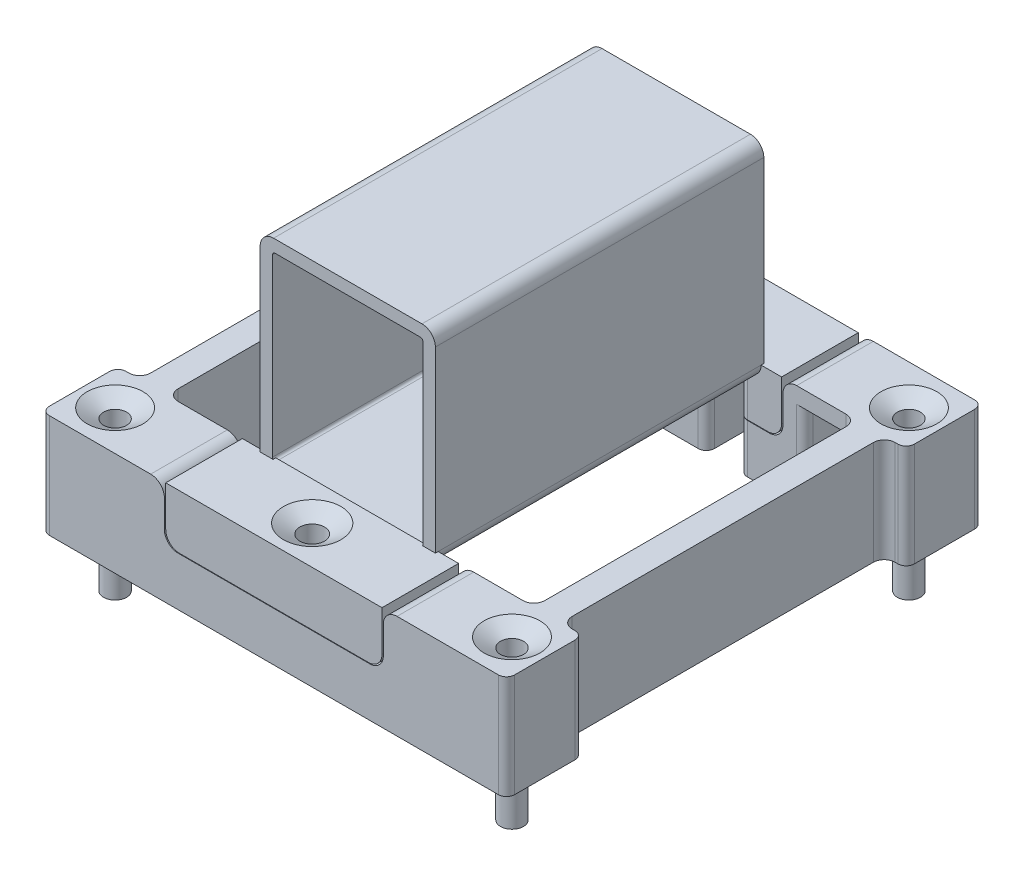
SolidWorks part; units mm, degrees
ref_plane "Front Plane" through (0, 0, 0) normal (0, 0, 1) x (1, 0, 0)
ref_plane "Top Plane" through (0, 0, 0) normal (0, 1, 0) x (1, 0, 0)
ref_plane "Right Plane" through (0, 0, 0) normal (1, 0, 0) x (0, 0, -1)
sketch "Sketch1" plane through (0, 0, 0) normal (0, 0, 1) x (1, 0, 0)
  line L0 (14.75, -16.3) -> (14.75, 16.3) construction
  line L1 (13.55, -17.5) -> (-13.55, -17.5) construction
  line L2 (-14.75, -16.3) -> (-14.75, 16.3) construction
  line L3 (13.55, 17.5) -> (-13.55, 17.5) construction
  line L4 (14.75, -16.3) -> (14.75, 16.3)
  line L5 (13.55, -17.5) -> (-13.55, -17.5)
  line L6 (-14.75, -16.3) -> (-14.75, 16.3)
  line L7 (13.55, 17.5) -> (-13.55, 17.5)
  line L8 (13.5, -16.25) -> (13.5, 16.25) construction
  line L9 (13.5, -16.25) -> (-13.5, -16.25) construction
  line L10 (-13.5, -16.25) -> (-13.5, 16.25) construction
  line L11 (13.5, 16.25) -> (-13.5, 16.25) construction
  line L12 (13.5, -16.25) -> (13.5, 16.25) construction
  line L13 (13.5, -16.25) -> (-13.5, -16.25) construction
  line L14 (-13.5, -16.25) -> (-13.5, 16.25) construction
  line L15 (13.5, 16.25) -> (-13.5, 16.25) construction
  line L16 (13.75, -16.5) -> (13.75, 16.5)
  line L17 (13.75, 16.5) -> (-13.75, 16.5)
  line L18 (-13.75, -16.5) -> (-13.75, 16.5)
  line L19 (13.75, -16.5) -> (-13.75, -16.5)
  arc A0 (14.75, 16.3) -> (13.55, 17.5) centre (13.55, 16.3) ccw construction
  arc A1 (13.55, -17.5) -> (14.75, -16.3) centre (13.55, -16.3) ccw construction
  arc A2 (-14.75, -16.3) -> (-13.55, -17.5) centre (-13.55, -16.3) ccw construction
  arc A3 (-13.55, 17.5) -> (-14.75, 16.3) centre (-13.55, 16.3) ccw construction
  arc A4 (14.75, 16.3) -> (13.55, 17.5) centre (13.55, 16.3) ccw
  arc A5 (13.55, -17.5) -> (14.75, -16.3) centre (13.55, -16.3) ccw
  arc A6 (-14.75, -16.3) -> (-13.55, -17.5) centre (-13.55, -16.3) ccw
  arc A7 (-13.55, 17.5) -> (-14.75, 16.3) centre (-13.55, 16.3) ccw
  dimension "D1" = 0.25
extrude "Boss-Extrude1" add sketch "Sketch1" along normal mid plane 60
sketch "Sketch2" plane through (0, 0, 0) normal (1, 0, 0) x (0, 0, -1)
  line L0 (-29.5, -24.25) -> (-29.5, 24.25) construction
  line L1 (-29.5, -16.3) -> (-43.5, -16.3)
  line L2 (-29.5, -16.3) -> (-29.5, -35.25)
  line L3 (-29.5, -35.25) -> (-43.5, -35.25)
  line L4 (-43.5, -16.3) -> (-43.5, -35.25)
  line L5 (-30, -16.3) -> (30, -16.3) construction
  line L6 (-29.5, -29.25) -> (29.5, -29.25) construction
  line L8 (-43.5, -15.125) -> (-43.5, 15.125) construction
  line L9 (0, 0) -> (0, -45.8115) construction
  line L10 (0, -15.125) -> (0, 15.125) construction
  line L11 (29.5, -35.25) -> (43.5, -35.25)
  line L12 (43.5, -16.3) -> (43.5, -35.25)
  line L13 (29.5, -16.3) -> (43.5, -16.3)
  line L14 (29.5, -16.3) -> (29.5, -35.25)
  dimension "D1" = 6
extrude "Boss-Extrude2" add sketch "Sketch2" along normal mid plane 85
sketch "Sketch3" plane through (0, -35.25, 0) normal (0, -1, 0) x (1, 0, 0)
  line L0 (0, 0) -> (59.8969, 0) construction
  line L1 (42.5, 29.5) -> (-42.5, 29.5) construction
  line L2 (-30, 29.5) -> (-24, 29.5)
  line L3 (-30, 29.5) -> (-30, 39.5)
  line L4 (-30, 39.5) -> (-24, 39.5)
  line L5 (-24, 29.5) -> (-24, 39.5)
  line L6 (-24.25, 29.5) -> (24.25, 29.5) construction
  line L7 (-12, 29.5) -> (-6, 29.5)
  line L8 (-12, 29.5) -> (-12, 39.5)
  line L9 (-12, 39.5) -> (-6, 39.5)
  line L10 (-6, 29.5) -> (-6, 39.5)
  line L11 (0, 0) -> (0, 46.5306) construction
  line L12 (30, 39.5) -> (24, 39.5)
  line L13 (24, 29.5) -> (24, 39.5)
  line L14 (30, 29.5) -> (24, 29.5)
  line L15 (30, 29.5) -> (30, 39.5)
  line L16 (12, 39.5) -> (6, 39.5)
  line L17 (6, 29.5) -> (6, 39.5)
  line L18 (12, 29.5) -> (6, 29.5)
  line L19 (12, 29.5) -> (12, 39.5)
  line L20 (12, -29.5) -> (12, -39.5)
  line L21 (12, -29.5) -> (6, -29.5)
  line L22 (6, -29.5) -> (6, -39.5)
  line L23 (12, -39.5) -> (6, -39.5)
  line L24 (30, -29.5) -> (30, -39.5)
  line L25 (30, -29.5) -> (24, -29.5)
  line L26 (24, -29.5) -> (24, -39.5)
  line L27 (30, -39.5) -> (24, -39.5)
  line L28 (-6, -29.5) -> (-6, -39.5)
  line L29 (-12, -39.5) -> (-6, -39.5)
  line L30 (-12, -29.5) -> (-12, -39.5)
  line L31 (-12, -29.5) -> (-6, -29.5)
  line L32 (-24, -29.5) -> (-24, -39.5)
  line L33 (-30, -39.5) -> (-24, -39.5)
  line L34 (-30, -29.5) -> (-30, -39.5)
  line L35 (-30, -29.5) -> (-24, -29.5)
  dimension "D1" = 12
  dimension "D2" = 12
  dimension "D3" = 6
  dimension "D4" = 6
  dimension "D5" = 10
extrude "Cut-Extrude1" cut sketch "Sketch3" against normal blind 16
fillet "Fillet1" radius 1.49 40 edges at (-24, -27.25, -39.5) (-6, -27.25, -39.5) (12, -27.25, -39.5) (30, -27.25, -39.5) (42.5, -25.775, -29.5) (42.5, -25.775, -43.5) (-42.5, -25.775, -43.5) (-42.5, -25.775, -29.5) (-30, -27.25, -29.5) (-30, -27.25, -39.5) (-24, -27.25, -29.5) (-12, -27.25, -29.5) (-12, -27.25, -39.5) (-6, -27.25, -29.5) (6, -27.25, -29.5) (6, -27.25, -39.5) (12, -27.25, -29.5) (24, -27.25, -29.5) (24, -27.25, -39.5) (30, -27.25, -29.5) (24, -27.25, 39.5) (6, -27.25, 39.5) (-12, -27.25, 39.5) (-30, -27.25, 39.5) (42.5, -25.775, 43.5) (42.5, -25.775, 29.5) (30, -27.25, 29.5) (30, -27.25, 39.5) (24, -27.25, 29.5) (12, -27.25, 29.5) (12, -27.25, 39.5) (6, -27.25, 29.5) (-6, -27.25, 29.5) (-6, -27.25, 39.5) (-12, -27.25, 29.5) (-24, -27.25, 29.5) (-24, -27.25, 39.5) (-30, -27.25, 29.5) (-42.5, -25.775, 43.5) (-42.5, -25.775, 29.5)
sketch "Sketch4" plane through (0, -16.3, 0) normal (0, 1, 0) x (1, 0, 0)
  line L0 (0, 0) -> (38.8928, 0) construction
  line L1 (-36.25, 36.25) -> (36.25, 36.25) construction
  line L2 (-36.25, 36.25) -> (-36.25, -36.25) construction
  line L3 (-36.25, -36.25) -> (36.25, -36.25) construction
  line L4 (36.25, 36.25) -> (36.25, -36.25) construction
  line L5 (-36.25, 36.25) -> (36.25, -36.25) construction
  line L6 (-36.25, -36.25) -> (36.25, 36.25) construction
  line L7 (0, 0) -> (0, -47.3346) construction
  circle A0 centre (36.25, -36.25) radius 2.1
  circle A1 centre (-36.25, -36.25) radius 2.1
  circle A2 centre (-36.25, 36.25) radius 2.1
  circle A3 centre (36.25, 36.25) radius 2.1
  point P0 (0, 0)
  dimension "D3" = 4.2
  dimension "D1" = 72.5
  dimension "D2" = 72.5
extrude "Cut-Extrude2" cut sketch "Sketch4" against normal through all both and the other way through all
chamfer "Chamfer1" distance 3 angle 30 4 edges at (36.25, -16.3, -38.35) (-36.25, -16.3, -38.35) (-36.25, -16.3, 34.15) (36.25, -16.3, 34.15) first distance on face at (36.25, -16.3, -38.35) first distance on face at (-36.25, -16.3, 34.15)
sketch "Sketch5" plane through (0, 0, -29.5) normal (0, 0, 1) x (1, 0, 0)
  line L0 (-14.75, -16.3) -> (-41.01, -16.3) construction
  line L1 (-38.5, -16.3) -> (-33.5, -16.3)
  line L2 (-38.5, -16.3) -> (-38.5, -35.25)
  line L3 (-38.5, -35.25) -> (-33.5, -35.25)
  line L4 (-33.5, -16.3) -> (-33.5, -35.25)
  line L5 (-31.49, -35.25) -> (-41.01, -35.25) construction
  line L6 (-42.5, -35.25) -> (-42.5, -16.3) construction
  line L7 (0, 0) -> (0, -37.6996) construction
  line L8 (33.5, -16.3) -> (33.5, -35.25)
  line L9 (38.5, -35.25) -> (33.5, -35.25)
  line L10 (38.5, -16.3) -> (38.5, -35.25)
  line L11 (38.5, -16.3) -> (33.5, -16.3)
  dimension "D1" = 4
  dimension "D2" = 5
extrude "Boss-Extrude3" add sketch "Sketch5" along normal up to surface (59 mm away) up to face at (0, -25.2999, 29.5)
fillet "Fillet2" radius 2 8 edges at (33.5, -25.775, 29.5) (38.5, -25.775, 29.5) (33.5, -25.775, -29.5) (38.5, -25.775, -29.5) (-38.5, -25.775, -29.5) (-33.5, -25.775, -29.5) (-33.5, -25.775, 29.5) (-38.5, -25.775, 29.5)
sketch "Sketch6" plane through (0, -35.25, 0) normal (0, -1, 0) x (1, 0, 0)
  circle A0 centre (-36.25, 36.25) radius 2.1 construction
  circle A1 centre (36.25, 36.25) radius 2.1 construction
  circle A2 centre (36.25, -36.25) radius 2.1 construction
  circle A3 centre (-36.25, -36.25) radius 2.1 construction
  circle A4 centre (-36.25, 36.25) radius 2.1
  circle A5 centre (36.25, 36.25) radius 2.1
  circle A6 centre (36.25, -36.25) radius 2.1
  circle A7 centre (-36.25, -36.25) radius 2.1
extrude "Boss-Extrude4" add sketch "Sketch6" along normal blind 10 and the other way blind 10 separate body
sketch "Sketch7" plane through (0, 0, 0) normal (0, 0, 1) x (1, 0, 0)
  line L0 (-20, -16.3) -> (-20, -26.3)
  line L1 (-20, -26.3) -> (20, -26.3)
  line L2 (20, -26.3) -> (20, -16.3)
  line L3 (-20, -16.3) -> (-19.75, -16.3)
  line L4 (-19.75, -16.3) -> (-19.75, -26.2)
  line L5 (-19.75, -26.2) -> (19.75, -26.2)
  line L6 (0, 25.3257) -> (0, -43.9694) construction
  line L8 (19.75, -26.2) -> (19.75, -16.3)
  line L9 (19.75, -16.3) -> (20, -16.3)
  line L10 (41.01, -16.3) -> (-41.01, -16.3) construction
  dimension "D1" = 0.25
  dimension "D2" = 0.1
  dimension "D3" = 10
  dimension "D4" = 40
extrude "Cut-Extrude3" cut sketch "Sketch7" against normal through all both and the other way through all
fillet "Fillet3" radius 2.5 8 edges at (-20, -16.3, 36.5) (-20, -26.3, 36.5) (20, -16.3, 36.5) (20, -26.3, 36.5) (20, -26.3, -36.5) (20, -16.3, -36.5) (-20, -16.3, -36.5) (-20, -26.3, -36.5)
fillet "Fillet4" radius 2.5 4 edges at (-19.75, -26.2, -36.5) (19.75, -26.2, -36.5) (19.75, -26.2, 36.5) (-19.75, -26.2, 36.5)
sketch "Sketch8" plane through (0, 0, 0) normal (0, 1, 0) x (1, 0, 0)
  line L0 (0, 0) -> (0, 46.4505) construction
  line L1 (0, 0) -> (50.2546, 0) construction
  line L2 (42.5, 36.5) -> (-42.5, 36.5) construction
  line L3 (42.5, 42.01) -> (42.5, 30.99) construction
  line L4 (-42.5, 42.01) -> (-42.5, 30.99) construction
  circle A0 centre (0, 36.5) radius 2.25
  circle A1 centre (0, -36.5) radius 2.25
  dimension "D1" = 4.5
extrude "Cut-Extrude4" cut sketch "Sketch8" against normal through all both and the other way through all
sketch "Sketch9" plane through (0, -35.25, 0) normal (0, -1, 0) x (1, 0, 0)
  line L0 (0, 0) -> (47.2104, 0) construction
  line L1 (0, 32.4008) -> (3.55, 34.4504)
  line L2 (3.55, 34.4504) -> (3.55, 38.5496)
  line L3 (3.55, 38.5496) -> (0, 40.5992)
  line L4 (0, 40.5992) -> (-3.55, 38.5496)
  line L5 (-3.55, 38.5496) -> (-3.55, 34.4504)
  line L6 (-3.55, 34.4504) -> (0, 32.4008)
  line L7 (-3.55, -34.4504) -> (0, -32.4008)
  line L8 (-3.55, -38.5496) -> (-3.55, -34.4504)
  line L9 (0, -40.5992) -> (-3.55, -38.5496)
  line L10 (3.55, -38.5496) -> (0, -40.5992)
  line L11 (3.55, -34.4504) -> (3.55, -38.5496)
  line L12 (0, -32.4008) -> (3.55, -34.4504)
  circle A0 centre (0, 36.5) radius 3.55 construction
  dimension "D1" = 7.1
extrude "Cut-Extrude5" cut sketch "Sketch9" against normal blind 4
chamfer "Chamfer3" distance 3 angle 30 2 edges at (0, -16.3, 34.25) (0, -16.3, -38.75) first distance on face at (0, -16.3, 34.25) first distance on face at (0, -16.3, -38.75)
sketch "Sketch10" plane through (0, 0, 0) normal (0, 0, 1) x (1, 0, 0)
  line L3 (13.55, -18.75) -> (-13.55, -18.75)
  line L4 (-14.5, 16.3) -> (-14.5, -16.3)
  line L5 (13.55, -17.25) -> (-13.55, -17.25)
  line L9 (16, -16.3) -> (16, 16.3)
  line L10 (13.55, 18.75) -> (-13.55, 18.75)
  line L11 (-16, 16.3) -> (-16, -16.3)
  line L12 (14.5, -16.3) -> (14.5, 16.3)
  line L14 (13.55, 17.25) -> (-13.55, 17.25)
  arc A2 (-14.5, -16.3) -> (-13.55, -17.25) centre (-13.55, -16.3) ccw
  arc A3 (13.55, -17.25) -> (14.5, -16.3) centre (13.55, -16.3) ccw
  arc A6 (16, 16.3) -> (13.55, 18.75) centre (13.55, 16.3) ccw
  arc A7 (-13.55, 18.75) -> (-16, 16.3) centre (-13.55, 16.3) ccw
  arc A9 (-16, -16.3) -> (-13.55, -18.75) centre (-13.55, -16.3) ccw
  arc A10 (14.5, 16.3) -> (13.55, 17.25) centre (13.55, 16.3) ccw
  arc A12 (13.55, -18.75) -> (16, -16.3) centre (13.55, -16.3) ccw
  arc A13 (-13.55, 17.25) -> (-14.5, 16.3) centre (-13.55, 16.3) ccw
  dimension "D4" = 1.5
extrude "Boss-Extrude5" add sketch "Sketch10" along direction (0, 0, -1) on the side of the normal mid plane 60
fillet "Fillet5" radius 0.5 4 edges at (13.75, -16.5, 0) (13.75, 16.5, 0) (-13.75, 16.5, 0) (-13.75, -16.5, 0)
